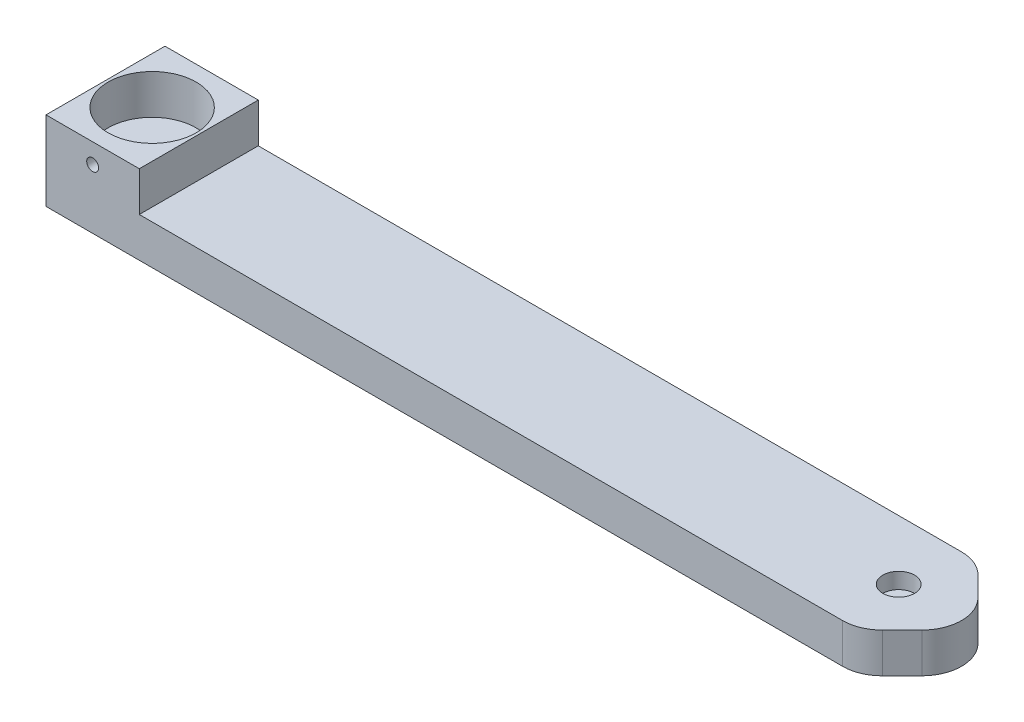
SolidWorks part; units mm, degrees
ref_plane "Front Plane" through (0, 0, 0) normal (0, 0, 1) x (1, 0, 0)
ref_plane "Top Plane" through (0, 0, 0) normal (0, 1, 0) x (1, 0, 0)
ref_plane "Right Plane" through (0, 0, 0) normal (1, 0, 0) x (0, 0, -1)
sketch "Sketch1" plane through (0, 0, 0) normal (0, 1, 0) x (1, 0, 0)
  line L1 (-110, -15) -> (110, -15)
  line L2 (-110, -15) -> (-110, 15)
  line L3 (-110, 15) -> (110, 15)
  line L4 (110, -15) -> (110, 15)
  line L5 (-110, -15) -> (110, 15) construction
  line L6 (-110, 15) -> (110, -15) construction
  point P0 (0, 0)
  dimension "D1" = 220
  dimension "D2" = 30
extrude "Boss-Extrude1" add sketch "Sketch1" along normal blind 10
sketch "Sketch2" plane through (0, 10, 0) normal (0, 1, 0) x (1, 0, 0)
  line L0 (-11, 0) -> (11, 0) construction
  line L2 (-86.4763, -15) -> (-110, -15)
  line L3 (-86.4763, -15) -> (-86.4763, 15)
  line L4 (-86.4763, 15) -> (-110, 15)
  line L5 (-110, -15) -> (-110, 15)
  line L6 (-86.4763, -15) -> (-110, 15) construction
  line L7 (-86.4763, 15) -> (-110, -15) construction
  circle A1 centre (-98.2382, 0) radius 11.1
  line M3 (110, 15) -> (-110, 15)
  line M4 (-110, 15) -> (-110, -15)
  line M5 (-110, -15) -> (110, -15)
  dimension "D2" = 22.2
extrude "Boss-Extrude3" add sketch "Sketch2" along normal blind 10 contours L3 A1 M5 M3 M4 region at (-98.2382, 10, 14.6188)
sketch "Sketch4" plane through (0, 10, 0) normal (0, 1, 0) x (1, 0, 0)
  line L0 (-11, 0) -> (11, 0) construction
  line L1 (110, -15) -> (110, 15) construction
  circle A0 centre (90, 0) radius 4
  dimension "D1" = 8
  dimension "D2" = 20
sketch "Sketch6" plane through (0, 0, 15) normal (0, 0, 1) x (1, 0, 0)
  line L0 (-86.4763, 10) -> (-110, 10) construction
  line L1 (-110, 20) -> (-110, 0) construction
  line L2 (-98.2382, 20) -> (-98.2382, 10) construction
  line L3 (-110, 20) -> (-86.4763, 20) construction
  circle A0 centre (-98.2382, 15) radius 1.5
  dimension "D1" = 3
extrude "Cut-Extrude2" cut sketch "Sketch6" against normal blind 10
extrude "Cut-Extrude3" cut sketch "Sketch4" against normal blind 4
sketch "Sketch7" plane through (0, 6, 0) normal (0, 1, 0) x (1, 0, 0)
  circle A0 centre (90, 0) radius 1.5
  dimension "D1" = 3
extrude "Cut-Extrude4" cut sketch "Sketch7" against normal blind 14
sketch "Sketch8" plane through (0, 10, 0) normal (0, 1, 0) x (1, 0, 0)
  line L0 (95, 15) -> (110, 0)
  line L1 (110, 15) -> (-86.4763, 15) construction
  line L2 (110, -15) -> (110, 15) construction
  line L4 (110, 0) -> (95, -15)
  line L5 (-86.4763, -15) -> (110, -15) construction
  line L6 (95, -15) -> (110, -15)
  line L7 (110, -15) -> (110, 0)
  line L8 (110, 0) -> (110, 15)
  line L9 (110, 15) -> (95, 15)
  line L11 (110, 15) -> (95, 15) construction
  line L12 (110, 15) -> (110, 0) construction
  line L13 (110, 0) -> (95, 0) construction
  line L14 (95, 15) -> (95, 0) construction
  line M11 (-86.4763, -15) -> (110, -15)
  line M12 (110, -15) -> (110, 15)
  line M13 (110, 15) -> (-86.4763, 15)
extrude "Cut-Extrude5" cut sketch "Sketch8" against normal blind 10 contours L4 M12 M11 | L0 M13 M12 region at (105, 10, -10) region at (105, 10, 10)
fillet "Fillet1" radius 10 3 edges at (95, 5, -15) (110, 5, 0) (95, 5, 15)
